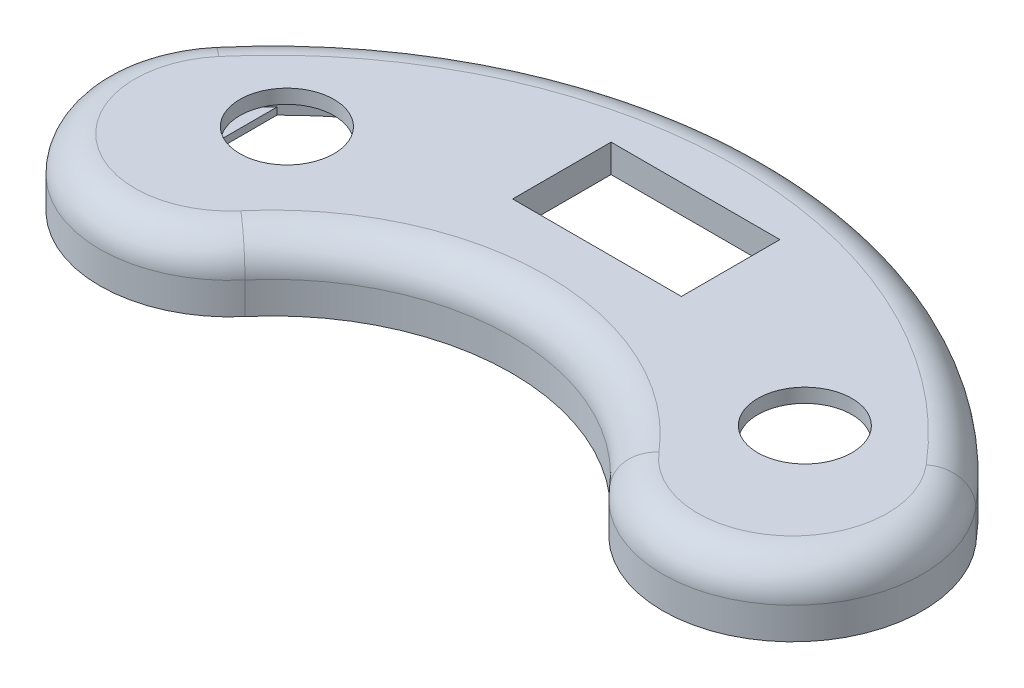
SolidWorks part; units mm, degrees
ref_plane "Front Plane" through (0, 0, 0) normal (0, 0, 1) x (1, 0, 0)
ref_plane "Top Plane" through (0, 0, 0) normal (0, 1, 0) x (1, 0, 0)
ref_plane "Right Plane" through (0, 0, 0) normal (1, 0, 0) x (0, 0, -1)
sketch "Sketch2" plane through (0, 0, 0) normal (0, 1, 0) x (1, 0, 0)
  arc A0 (-43.6936, 0) -> (57.9064, 0) centre (7.1064, -43.0279) cw construction
  arc A1 (73.8768, 13.527) -> (-59.6641, 13.527) centre (7.1064, -43.0279) ccw
  arc A2 (41.9359, -13.527) -> (-27.7232, -13.527) centre (7.1064, -43.0279) ccw
  arc A3 (41.9359, -13.527) -> (73.8768, 13.527) centre (57.9064, 0) ccw
  arc A4 (-59.6641, 13.527) -> (-27.7232, -13.527) centre (-43.6936, 0) ccw
  point P3 (7.1064, 23.5457)
  point P8 (7.1064, 2.6164)
  dimension "D1" = 50.8
  dimension "D2" = 50.8
extrude "Boss-Extrude1" add sketch "Sketch2" along normal blind 19.05
fillet "Fillet1" radius 3.81 4 edges at (7.1064, 19.05, -2.6164) (-57.2207, 19.05, 15.9704) (7.1064, 19.05, -44.475) (71.4334, 19.05, 15.9704)
fillet "Fillet2" radius 3.81 4 edges at (7.1064, 0, -44.475) (-57.2207, 0, 15.9704) (7.1064, 0, -2.6164) (71.4334, 0, 15.9704)
sketch "Sketch3" plane through (0, 19.05, 0) normal (0, 1, 0) x (1, 0, 0)
  line L1 (-56.7568, 11.0646) -> (70.9695, 11.0646) construction
  line L2 (-10.4904, 35.6265) -> (-10.4904, 12.7665)
  line L3 (-10.4904, 35.6265) -> (25.0696, 35.6265)
  line L4 (-10.4904, 12.7665) -> (25.0696, 12.7665)
  line L5 (25.0696, 35.6265) -> (25.0696, 12.7665)
  line L6 (-10.4904, 35.6265) -> (25.0696, 35.6265) construction
  point P16 (7.2896, 35.6265)
  dimension "D1" = 22.86
  dimension "D2" = 35.56
extrude "Cut-Extrude1" cut sketch "Sketch3" against normal blind 2.54 contours L2 L4 L5 L3
shell "Shell7" thickness 2.54 removed face at (7.2896, 16.51, -24.1965) outward yes
sketch "Sketch6" plane through (0, 21.59, 0) normal (0, 1, 0) x (1, 0, 0)
  line L0 (53.8552, 6.2606) -> (80.5252, 6.2606) construction
  line L1 (-39.6425, 6.2606) -> (-66.3125, 6.2606) construction
  circle A0 centre (-39.6425, 6.2606) radius 8.5
  arc A1 (-61.6022, 15.1687) -> (-25.785, -15.1687) centre (-43.6936, 0) ccw construction
  circle A2 centre (53.8552, 6.2606) radius 8.5
  arc A3 (39.9978, -15.1687) -> (75.815, 15.1687) centre (57.9064, 0) ccw construction
  dimension "D1" = 26.67
  dimension "D2" = 26.67
extrude "Cut-Extrude2" cut sketch "Sketch6" against normal blind 2.54
ref_plane "Plane1" through (0, 9.525, 0) normal (0, 1, 0) x (1, 0, 0)
other "SurfaceCut1"
sketch "Sketch7" plane through (0, 9.525, 0) normal (0, 1, 0) x (1, 0, 0)
  line L0 (71.1404, 19.1922) -> (71.1404, -18.7862)
  line L1 (71.1404, -18.7862) -> (68.6004, -20.1465)
  line L2 (71.1404, 19.1922) -> (68.6004, 22.0215)
  line L3 (68.6004, -20.1465) -> (68.6004, 22.0215)
  line L4 (81.3004, 1.878) -> (-67.0877, 1.878) construction
  line L5 (-54.3877, 22.0215) -> (-56.9277, 19.1922)
  line L6 (-56.9277, 19.1922) -> (-56.9277, -18.7862)
  line L7 (-56.9277, -18.7862) -> (-54.3877, -20.5438)
  line L8 (-54.3877, -20.5438) -> (-54.3877, 22.0215)
  arc A0 (39.9978, -15.1687) -> (75.815, 15.1687) centre (57.9064, 0) ccw construction
  arc A1 (-61.6022, 15.1687) -> (-25.785, -15.1687) centre (-43.6936, 0) ccw construction
  point P7 (-26.4942, 26.9386)
  point P17 (-54.2474, -20.5438)
  dimension "D1" = 2.54
  dimension "D2" = 10.16
  dimension "D3" = 10.16
  dimension "D4" = 2.54
extrude "Boss-Extrude3" add sketch "Sketch7" along normal blind 1.27
